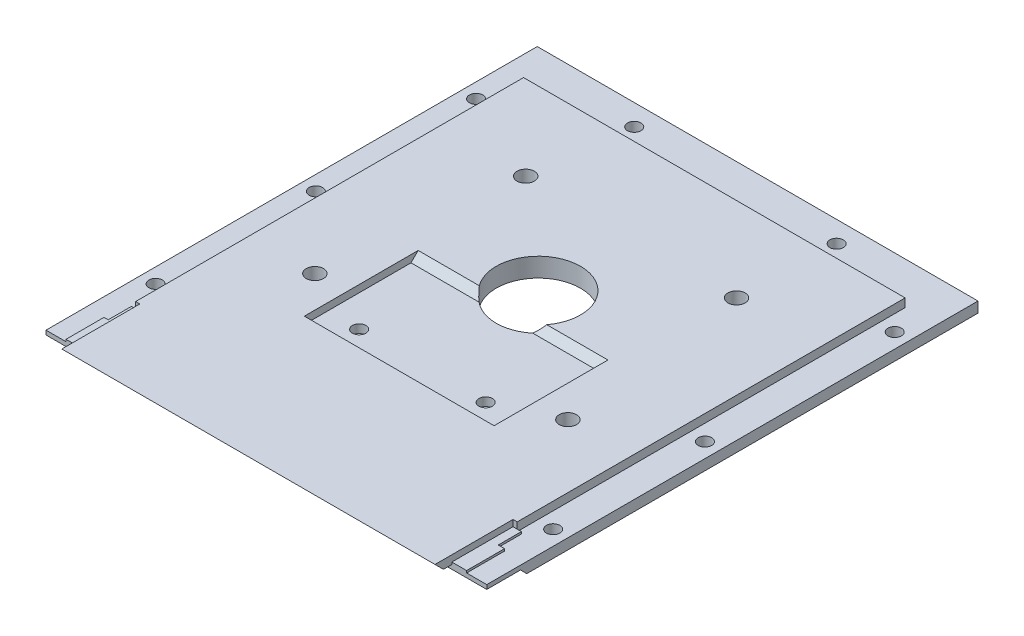
SolidWorks part; units mm, degrees
ref_plane "前视基准面" through (0, 0, 0) normal (0, 0, 1) x (1, 0, 0)
ref_plane "上视基准面" through (0, 0, 0) normal (0, 1, 0) x (1, 0, 0)
ref_plane "右视基准面" through (0, 0, 0) normal (1, 0, 0) x (0, 0, -1)
other "Configuration Table"
sketch "草图1" plane through (0, 0, 0) normal (0, 1, 0) x (1, 0, 0)
  line L1 (0, 0) -> (90.5, 0)
  line L2 (0, 0) -> (0, 97)
  line L3 (0, 97) -> (90.5, 97)
  line L4 (90.5, 0) -> (90.5, 97)
  dimension "D1" = 90.5
  dimension "D2" = 97
extrude "凸台-拉伸1" add sketch "草图1" along normal blind 2
sketch "草图2" plane through (0, 0, 0) normal (0, -1, 0) x (1, 0, 0)
  line L0 (45.25, 0) -> (45.25, -97) construction
  line L1 (0, 0) -> (90.5, 0) construction
  line L2 (90.5, -97) -> (0, -97) construction
  line L3 (-3.25, -13) -> (-3.25, -89) construction
  line L4 (-6.75, 17) -> (97.775, 17)
  line L5 (-6.75, 17) -> (-6.75, -107)
  line L6 (-6.75, -107) -> (97.775, -107)
  line L7 (97.775, 17) -> (97.775, -107)
  line L8 (94.275, -90.75) -> (94.275, -9.75) construction
  circle A0 centre (21.25, -102) radius 1.6
  circle A1 centre (69.25, -102) radius 1.6
  circle A2 centre (-3.25, -89) radius 1.6
  circle A3 centre (94.275, -90.75) radius 1.6
  circle A4 centre (-3.25, -13) radius 1.6
  circle A5 centre (-3.25, -51) radius 1.6
  circle A6 centre (94.275, -9.75) radius 1.6
  circle A7 centre (94.275, -45.75) radius 1.6
  dimension "D1" = 3.2
  dimension "D2" = 48
  dimension "D3" = 5
  dimension "D4" = 5
  dimension "D5" = 24.5
  dimension "D6" = 3.5
  dimension "D7" = 13
  dimension "D8" = 25.025
  dimension "D9" = 11.25
  dimension "D11" = 38
  dimension "D12" = 45
  dimension "D13" = 36
  dimension "D10" = 3.5
  dimension "D14" = 114
extrude "凸台-拉伸2" add sketch "草图2" along normal blind 2.5
sketch "草图3" plane through (0, 0, 0) normal (0, 1, 0) x (1, 0, 0)
  line L0 (0, 0) -> (90.5, 0) construction
  line L1 (1, 0) -> (89.5, 0)
  line L2 (1, 0) -> (1, -17)
  line L3 (1, -17) -> (89.5, -17)
  line L4 (89.5, 0) -> (89.5, -17)
  line L5 (97.775, -17) -> (-6.75, -17) construction
  line L6 (0, 97) -> (0, 0) construction
  line L7 (90.5, 0) -> (90.5, 97) construction
  dimension "D1" = 1
  dimension "D2" = 1
extrude "凸台-拉伸3" add sketch "草图3" along normal up to surface (2 mm away) up to face at (45.25, 2, -48.5)
sketch "草图4" plane through (0, 0, 0) normal (0, 1, 0) x (1, 0, 0)
  line L0 (0, 97) -> (0, 0) construction
  line L1 (1, 0) -> (0, 0)
  line L2 (1, 0) -> (1, 5)
  line L3 (1, 5) -> (0, 5)
  line L4 (0, 0) -> (0, 5)
  line L5 (90.5, 0) -> (90.5, 97) construction
  line L6 (89.5, 0) -> (90.5, 0)
  line L7 (89.5, 0) -> (89.5, 5)
  line L8 (89.5, 5) -> (90.5, 5)
  line L9 (90.5, 0) -> (90.5, 5)
  dimension "D1" = 5
extrude "切除-拉伸1" cut sketch "草图4" along normal up to surface (2 mm away) up to face at (45.25, 2, -20)
sketch "草图5" plane through (97.775, 0, 0) normal (1, 0, 0) x (0, 0, -1)
  line L0 (-8.5, -2.5) -> (-8.5, 0)
  line L1 (107, -2.5) -> (-17, -2.5) construction
  line L2 (107, 0) -> (-17, 0) construction
  line L4 (5, 2) -> (-17, 2) construction
  line L5 (-11.5, 2) -> (-17, 2)
  line L6 (-17, 2) -> (-17, -2.5)
  line L7 (-17, -2.5) -> (-8.5, -2.5)
  line L8 (-11.5, 2) -> (-9.5, 0)
  line L9 (-17, 0) -> (5, 0) construction
  line L10 (-9.5, 0) -> (-8.5, 0)
  dimension "D1" = 8.5
  dimension "D2" = 1
  dimension "D3" = 45
extrude "切除-拉伸2" cut sketch "草图5" against normal through all
sketch "草图6" plane through (0, 2, 0) normal (0, 1, 0) x (1, 0, 0)
  line L0 (45.5125, 107) -> (45.5125, 47) construction
  line L1 (68.0125, 22) -> (23.0125, 22)
  line L2 (68.0125, 22) -> (68.0125, 47)
  line L3 (68.0125, 47) -> (23.0125, 47)
  line L4 (23.0125, 22) -> (23.0125, 47)
  line L5 (-6.75, 107) -> (97.775, 107) construction
  line L7 (90.5, 97) -> (0, 97) construction
  dimension "D1" = 25
  dimension "D2" = 45
  dimension "D3" = 50
extrude "切除-拉伸3" cut sketch "草图6" against normal blind 1.7
sketch "草图7" plane through (0, 0.3, 0) normal (0, 1, 0) x (1, 0, 0)
  line L0 (23.0125, 27.5) -> (68.0125, 27.5) construction
  line L1 (23.0125, 47) -> (23.0125, 22) construction
  line L2 (68.0125, 22) -> (68.0125, 47) construction
  line L3 (23.0125, 22) -> (68.0125, 22) construction
  line L4 (45.5125, 47) -> (45.5125, 22) construction
  line L5 (68.0125, 47) -> (23.0125, 47) construction
  line L6 (23.0125, 22) -> (68.0125, 22) construction
  circle A0 centre (30.5125, 27.5) radius 1.6
  circle A1 centre (60.5125, 27.5) radius 1.6
  dimension "D2" = 30
  dimension "D3" = 3.2
  dimension "D1" = 5.5
extrude "切除-拉伸4" cut sketch "草图7" against normal up to next
chamfer "倒角1" distance 2 angle 45 1 edges at (45.5125, 2, -47)
sketch "草图8" plane through (0, 2, 0) normal (0, 1, 0) x (1, 0, 0)
  line L0 (45.5125, 107) -> (45.5125, -11.5) construction
  line L1 (-6.75, 107) -> (97.775, 107) construction
  line L3 (20.5125, 77) -> (70.5125, 77) construction
  line L4 (1, -11.5) -> (89.5, -11.5) construction
  line L5 (90.5, 97) -> (0, 97) construction
  circle A0 centre (20.5125, 77) radius 2.05
  circle A1 centre (70.5125, 77) radius 2.05
  circle A2 centre (15.5125, 32) radius 2.05
  circle A3 centre (75.5125, 32) radius 2.05
  dimension "D1" = 4.1
  dimension "D4" = 60
  dimension "D2" = 50
  dimension "D3" = 20
  dimension "D5" = 45
extrude "切除-拉伸5" cut sketch "草图8" against normal up to next
sketch "草图9" plane through (0, 2, 0) normal (0, 1, 0) x (1, 0, 0)
  line L0 (45.5125, 107) -> (45.5125, 55) construction
  line L1 (-6.75, 107) -> (97.775, 107) construction
  circle A0 centre (45.5125, 55) radius 10
  dimension "D1" = 20
  dimension "D2" = 52
extrude "切除-拉伸6" cut sketch "草图9" against normal up to next
sketch "草图10" plane through (0, -2.5, 0) normal (0, -1, 0) x (1, 0, 0)
  line L1 (27.7625, -25.9123) -> (27.7625, -29.0877)
  line L2 (27.7625, -29.0877) -> (30.5125, -30.6754)
  line L3 (30.5125, -30.6754) -> (33.2625, -29.0877)
  line L4 (33.2625, -29.0877) -> (33.2625, -25.9123)
  line L5 (33.2625, -25.9123) -> (30.5125, -24.3246)
  line L6 (30.5125, -24.3246) -> (27.7625, -25.9123)
  line L7 (57.7625, -25.9123) -> (57.7625, -29.0877)
  line L8 (57.7625, -29.0877) -> (60.5125, -30.6754)
  line L9 (60.5125, -30.6754) -> (63.2625, -29.0877)
  line L10 (63.2625, -29.0877) -> (63.2625, -25.9123)
  line L11 (63.2625, -25.9123) -> (60.5125, -24.3246)
  line L12 (60.5125, -24.3246) -> (57.7625, -25.9123)
  circle A0 centre (30.5125, -27.5) radius 2.75 construction
  circle A1 centre (60.5125, -27.5) radius 2.75 construction
  dimension "D1" = 5.5
extrude "切除-拉伸7" cut sketch "草图10" against normal blind 0.8
sketch "草图11" plane through (97.775, 0, 0) normal (1, 0, 0) x (0, 0, -1)
  line L0 (107, -2.5) -> (-8.5, -2.5) construction
  line L1 (-8.5, 0) -> (-2, 0)
  line L2 (-8.5, 0) -> (-8.5, -2.5)
  line L3 (-8.5, -2.5) -> (-2, -2.5)
  line L4 (-2, 0) -> (-2, -2.5)
  dimension "D1" = 6.5
extrude "切除-拉伸8" cut sketch "草图11" against normal up to next
chamfer "倒角2" distance 2 angle 45 1 edges at (45.5125, -2.5, 2)
sketch "草图12" plane through (0, 0, 0) normal (0, -1, 0) x (1, 0, 0)
  line L0 (1, 9.5) -> (89.5, 9.5) construction
  line L1 (-6.75, 0) -> (97.775, 0)
  line L2 (-6.75, 0) -> (-6.75, 9.5)
  line L3 (-6.75, 9.5) -> (97.775, 9.5)
  line L4 (97.775, 0) -> (97.775, 9.5)
  line L6 (97.775, 0) -> (-6.75, 0) construction
extrude "凸台-拉伸4" add sketch "草图12" along normal blind 1
sketch "草图13" plane through (0, 0, 0) normal (0, 1, 0) x (1, 0, 0)
  line L0 (1, -11.5) -> (1, 5) construction
  line L1 (1, 5) -> (-1, 5)
  line L2 (1, 5) -> (1, -9.5)
  line L3 (1, -9.5) -> (-1, -9.5)
  line L4 (-1, 5) -> (-1, -9.5)
  line L5 (89.5, 5) -> (91.5, 5)
  line L6 (89.5, 5) -> (89.5, -9.5)
  line L7 (89.5, -9.5) -> (91.5, -9.5)
  line L8 (91.5, 5) -> (91.5, -9.5)
  line L9 (1, -9.5) -> (-6.75, -9.5) construction
  dimension "D1" = 2
  dimension "D2" = 2
extrude "凸台-拉伸5" add sketch "草图13" along normal blind 0.5
sketch "草图14" plane through (0, 0, 0) normal (0, 1, 0) x (1, 0, 0)
  line L0 (97.775, -9.5) -> (91.5, -9.5) construction
  line L1 (93, -9.5) -> (91.5, -9.5)
  line L2 (93, -9.5) -> (93, -0.5)
  line L3 (93, -0.5) -> (91.5, -0.5)
  line L4 (91.5, -9.5) -> (91.5, -0.5)
  line L6 (-1, -9.5) -> (-6.75, -9.5) construction
  line L7 (-2, -9.5) -> (-1, -9.5)
  line L8 (-2, -9.5) -> (-2, -0.5)
  line L9 (-2, -0.5) -> (-1, -0.5)
  line L10 (-1, -9.5) -> (-1, -0.5)
  line L11 (-1, 5) -> (-1, -9.5) construction
  line L12 (91.5, -9.5) -> (91.5, 5) construction
  dimension "D1" = 1
  dimension "D2" = 1.5
  dimension "D3" = 9
extrude "凸台-拉伸6" add sketch "草图14" along normal up to surface (0.5 mm away) up to face at (0, 0.5, 0.8)
sketch "草图15" plane through (0, -4.75, 4.75) normal (0, -0.7071, 0.7071) x (1, 0, 0)
  line L4 (89.5, 9.5459) -> (1, 9.5459)
  line L5 (1, 9.5459) -> (1, 6.7175)
  line L6 (1, 6.7175) -> (89.5, 6.7175)
  line L7 (89.5, 6.7175) -> (89.5, 9.5459)
  line L8 (89.5, 9.5459) -> (1, 9.5459)
  line L9 (1, 9.5459) -> (1, 6.7175)
  line L10 (1, 6.7175) -> (89.5, 6.7175)
  line L11 (89.5, 6.7175) -> (89.5, 9.5459)
  dimension "D1" = 0
extrude "凸台-拉伸7" add sketch "草图15" along direction (0, 0, 1) on the side of the normal blind 2
